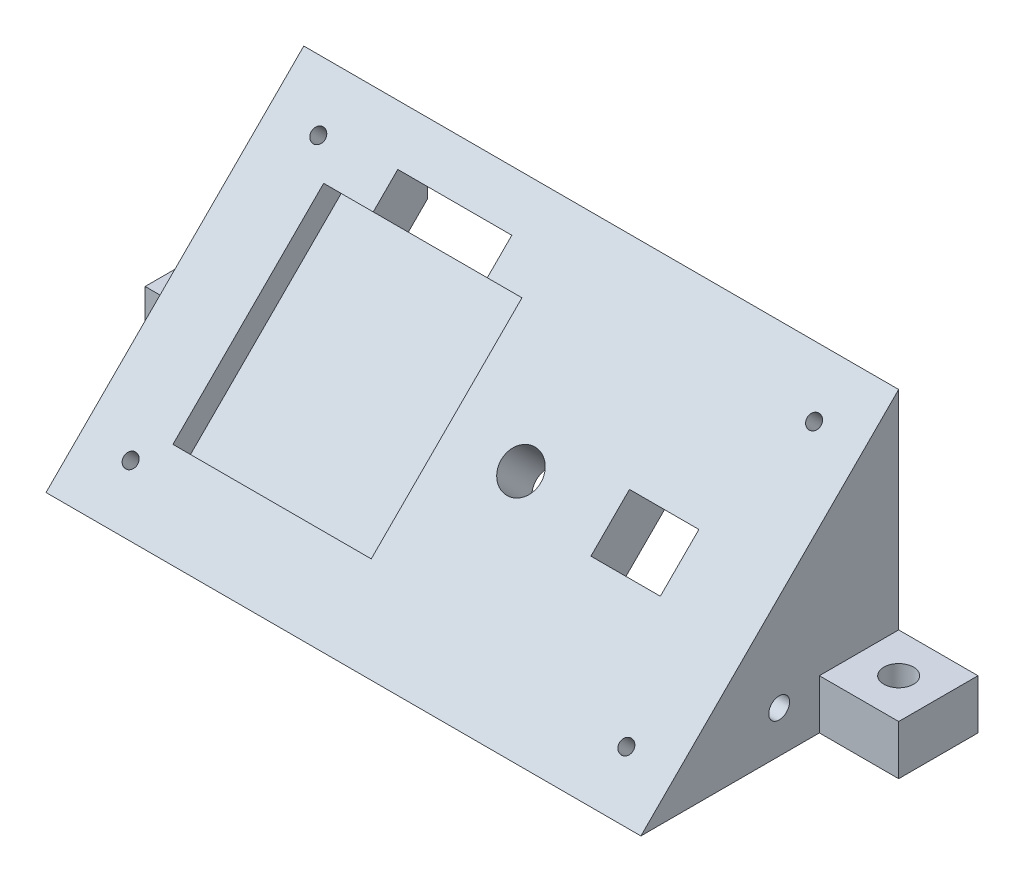
SolidWorks part; units mm, degrees
note: The reader was unsure of these and kept them because the rebuilt part matched: shared geometry of "Эскиз4<3>".
ref_plane "Спереди" through (0, 0, 0) normal (0, 0, 1) x (1, 0, 0)
ref_plane "Сверху" through (0, 0, 0) normal (0, 1, 0) x (1, 0, 0)
ref_plane "Справа" through (0, 0, 0) normal (1, 0, 0) x (0, 0, -1)
sketch "Эскиз3" plane through (0, 0, 0) normal (1, 0, 0) x (0, 0, -1)
  line L0 (0, 0) -> (52, 0)
  line L1 (52, 0) -> (52, 52)
  line L2 (52, 52) -> (0, 0)
extrude "Бобышка-Вытянуть3" add sketch "Эскиз3" along normal blind 120
ref_plane "Плоскость5" through (0, 0, 0) normal (0, 0.7071, 0.7071) x (1, 0, 0)
sketch "Эскиз4" plane through (0, 0, 0) normal (0, 0.7071, 0.7071) x (1, 0, 0)
  line L0 (88, 42) -> (102, 42)
  line L2 (15, 15) -> (15, 58)
  line L3 (15, 58) -> (25, 58)
  line L4 (25, 58) -> (25, 65)
  line L5 (15, 15) -> (55, 15)
  line L6 (55, 15) -> (55, 58)
  line L7 (55, 58) -> (48, 58)
  line L8 (48, 58) -> (48, 65)
  line L9 (48, 65) -> (25, 65)
  line L11 (102, 42) -> (102, 31)
  line L12 (102, 31) -> (88, 31)
  line L13 (88, 31) -> (88, 42)
  circle A0 centre (70, 36.5) radius 4
extrude "Вырез-Вытянуть1" cut sketch "Эскиз4" against normal blind 120 contours A0 | L13 L12 L11 L0
extrude "Вырез-Вытянуть2" cut sketch "Эскиз4<3>" against normal blind 5 contours L8 L9 L4 L3 L2 L5 L6 L7
sketch "Эскиз4<3>" plane through (0, 0, 0) normal (0, 0.7071, 0.7071) x (1, 0, 0) same geometry as "Эскиз4"
ref_plane "Плоскость6" through (0, -3.5355, -3.5355) normal (0, 0.7071, 0.7071) x (1, 0, 0)
sketch "Эскиз5" plane through (0, -3.5355, -3.5355) normal (0, 0.7071, 0.7071) x (1, 0, 0)
  line L0 (25, 65) -> (25, 58)
  line L1 (25, 58) -> (48, 58)
  line L2 (48, 58) -> (48, 65)
  line L3 (48, 65) -> (25, 65)
extrude "Вырез-Вытянуть3" cut sketch "Эскиз5" against normal blind 98
ref_plane "Плоскость7" through (0, -7.0711, -7.0711) normal (0, 0.7071, 0.7071) x (1, 0, 0)
sketch "Эскиз6" plane through (0, -7.0711, -7.0711) normal (0, 0.7071, 0.7071) x (1, 0, 0)
  line L7 (110, 10) -> (110, 63.5391)
  line L8 (110, 63.5391) -> (10, 63.5391)
  line L9 (10, 63.5391) -> (10, 10)
  line L10 (10, 10) -> (110, 10)
extrude "Вырез-Вытянуть4" cut sketch "Эскиз6" against normal blind 98
sketch "Эскиз7" plane through (0, 0, 0) normal (0, 0.7071, 0.7071) x (1, 0, 0)
  circle A0 centre (10, 63.5391) radius 1.4
  circle A1 centre (110, 10) radius 1.4
  circle A2 centre (110, 63.5391) radius 1.4
  circle A3 centre (10, 10) radius 1.4
extrude "Вырез-Вытянуть5" cut sketch "Эскиз7" against normal blind 5
ref_plane "Плоскость12" through (0, 0, 0) normal (0, -1, 0) x (-1, 0, 0)
sketch "Эскиз13" plane through (0, 0, 0) normal (0, -1, 0) x (-1, 0, 0)
  line L0 (-120, 52) -> (-136, 52)
  line L1 (-136, 52) -> (-136, 36)
  line L2 (-136, 36) -> (-120, 36)
  line L3 (-120, 0) -> (-120, 52) construction
  line L4 (-120, 36) -> (-120, 52)
  line L5 (0, 52) -> (16, 52)
  line L6 (16, 52) -> (16, 36)
  line L7 (16, 36) -> (0, 36)
  line L8 (0, 0) -> (0, 52) construction
  line L9 (0, 36) -> (0, 52)
  circle A0 centre (-128, 44) radius 3
  circle A1 centre (8, 44) radius 3
extrude "Бобышка-Вытянуть8" add sketch "Эскиз13" against normal blind 10
ref_plane "Плоскость13" through (0, 0, 0) normal (-1, 0, 0) x (0, 0, 1)
sketch "Эскиз15" plane through (0, 0, 0) normal (-1, 0, 0) x (0, 0, 1)
  circle A0 centre (-27.8889, 8.434) radius 2.1
extrude "Вырез-Вытянуть7" cut sketch "Эскиз15" against normal through all both and the other way through all
